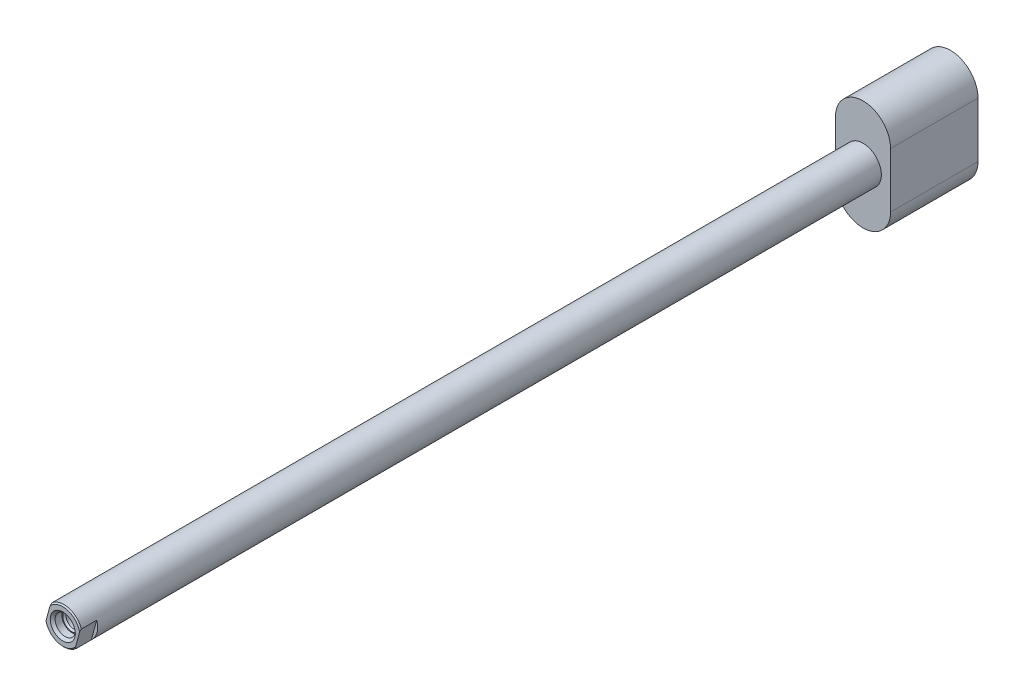
SolidWorks part; units mm, degrees
ref_plane "Front Plane" through (0, 0, 0) normal (0, 0, 1) x (1, 0, 0)
ref_plane "Top Plane" through (0, 0, 0) normal (0, 1, 0) x (1, 0, 0)
ref_plane "Right Plane" through (0, 0, 0) normal (1, 0, 0) x (0, 0, -1)
sketch "Sketch1" plane through (0, 0, 0) normal (1, 0, 0) x (0, 0, -1)
  line L0 (-7, 0) -> (-7, 2.8)
  line L1 (-7, 2.8) -> (-6.8, 3)
  line L2 (-6.8, 3) -> (138.15, 3)
  line L3 (138.15, 3) -> (138.15, 0)
  line L4 (138.15, 0) -> (-7, 0)
  line L5 (138.15, 0) -> (-7, 0) construction
revolve "Revolve1" add sketch "Sketch1" angle 360 about L5
sketch "Sketch2" plane through (0, 0, 0) normal (1, 0, 0) x (0, 0, -1)
  line L0 (-7, 0) -> (-7, 2.05)
  line L1 (-7, 2.05) -> (-6.6, 1.65)
  line L2 (-6.6, 1.65) -> (-5.5, 1.65)
  line L3 (-5.5, 1.65) -> (-5.5, 1.5)
  line L4 (-5.5, 1.5) -> (-5.2295, 1.2295)
  line L5 (-5.2295, 1.2295) -> (4, 1.2295)
  line L6 (4, 1.2295) -> (4.7099, 0)
  line L7 (4.7099, 0) -> (-7, 0)
  line L8 (4.7099, 0) -> (-7, 0) construction
revolve "Cut-Revolve1" cut sketch "Sketch2" angle 360 about L8
cosmetic thread "Cosmetic Thread1" parameters "D1"=6.5, "D2"=3
ref_plane "Plane1" through (0, 0, 7) normal (0, 0, 1) x (1, 0, 0)
ref_plane "Plane2" through (0, 0, 4.3) normal (0, 0, 1) x (1, 0, 0)
sketch "Sketch3" plane through (0, 0, 4.3) normal (0, 0, 1) x (1, 0, 0)
  line L0 (-6.4472, -4.7429) -> (3.212, -7.3311)
  line L1 (3.212, -7.3311) -> (5.8002, 2.3281)
  line L2 (5.8002, 2.3281) -> (3.3854, 2.9752)
  line L3 (3.3854, 2.9752) -> (1.1207, -5.4767)
  line L4 (1.1207, -5.4767) -> (-3.7089, -4.1826)
  line L5 (-3.7089, -4.1826) -> (-1.4442, 4.2693)
  line L6 (-1.4442, 4.2693) -> (-3.8591, 4.9163)
  line L7 (-3.8591, 4.9163) -> (-6.4472, -4.7429)
extrude "Cut-Extrude1" cut sketch "Sketch3" along normal blind 3.3
ref_plane "Plane3" through (0, 0, -269) normal (0, 0, 1) x (1, 0, 0)
ref_plane "Plane4" through (0, 0, -138.15) normal (0, 0, 1) x (1, 0, 0)
sketch "Sketch4" plane through (0, 0, -138.15) normal (0, 0, 1) x (1, 0, 0)
  line L0 (4.5, -4.5) -> (4.5, 4.5)
  line L1 (-4.5, 4.5) -> (-4.5, -4.5)
  arc A0 (-4.5, -4.5) -> (0, -9) centre (0, -4.5) ccw
  arc A1 (0, -9) -> (4.5, -4.5) centre (0, -4.5) ccw
  arc A2 (4.5, 4.5) -> (0, 9) centre (0, 4.5) ccw
  arc A3 (0, 9) -> (-4.5, 4.5) centre (0, 4.5) ccw
extrude "Boss-Extrude1" add sketch "Sketch4" along normal blind 14.3
ref_plane "kolben XY" through (0, 0, -138.15) normal (0, 0, 1) x (1, 0, 0)
ref_plane "kolben XZ" through (0, 0, 0) normal (0, -1, 0) x (-1, 0, 0)
ref_plane "kolben YZ" through (0, 0, 0) normal (1, 0, 0) x (0, 0, -1)
ref_axis "kolben X" through (-80.9, 0, -138.15) along (1, 0, 0)
ref_axis "kolben Y" through (0, -50, -138.15) along (0, 1, 0)
ref_axis "kolben Z" through (0, 0, 80.9) along (0, 0, -1)
sketch3d "kolben"
  point P0 (0, 0, -138.15)
